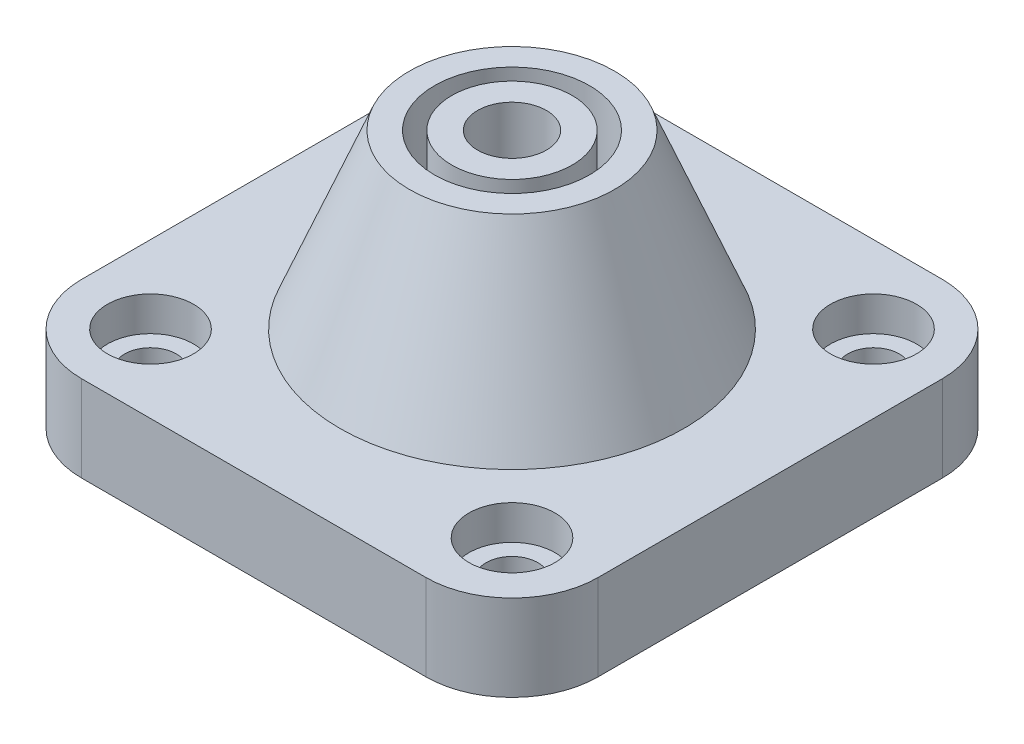
SolidWorks part; units mm, degrees
ref_plane "Front Plane" through (0, 0, 0) normal (0, 0, 1) x (1, 0, 0)
ref_plane "Top Plane" through (0, 0, 0) normal (0, 1, 0) x (1, 0, 0)
ref_plane "Right Plane" through (0, 0, 0) normal (1, 0, 0) x (0, 0, -1)
sketch "Sketch1" plane through (0, 0, 0) normal (0, 1, 0) x (1, 0, 0)
  line L1 (-15, -15) -> (15, -15)
  line L2 (-15, -15) -> (-15, 15)
  line L3 (-15, 15) -> (15, 15)
  line L4 (15, -15) -> (15, 15)
  line L5 (-15, -15) -> (15, 15) construction
  line L6 (-15, 15) -> (15, -15) construction
  point P0 (0, 0)
  dimension "D1" = 30
  dimension "D2" = 30
extrude "Boss-Extrude1" add sketch "Sketch1" along normal blind 5
sketch "Sketch4" plane through (0, 5, 0) normal (0, 1, 0) x (1, 0, 0)
  circle A0 centre (0, 0) radius 10
  dimension "D1" = 20
extrude "Boss-Extrude2" add sketch "Sketch4" along normal blind 10
sketch "Sketch5" plane through (0, 15, 0) normal (0, 1, 0) x (1, 0, 0)
  circle A0 centre (0, 0) radius 2
  dimension "D1" = 4
extrude "Cut-Extrude3" cut sketch "Sketch5" against normal through all both and the other way through all
sketch "Sketch6" plane through (0, 15, 0) normal (0, 1, 0) x (1, 0, 0)
  circle A0 centre (0, 0) radius 3.5
  circle A1 centre (0, 0) radius 4.5
  dimension "D1" = 7
  dimension "D2" = 9
extrude "Cut-Extrude4" cut sketch "Sketch6" against normal blind 7
chamfer "Chamfer1" distance 10 angle 22 1 edges at (0, 15, 10) first distance on face at (0, 15, 10)
sketch "Sketch8" plane through (0, 5, 0) normal (0, 1, 0) x (1, 0, 0)
  line L0 (-10.5, -1001.1158) -> (-10.5, 48998.8842) construction
  line L1 (10.5, -1001.594) -> (10.5, 48998.406) construction
  line L2 (-1000.2391, 10.5) -> (48999.7609, 10.5) construction
  line L3 (-998.9639, -10.5) -> (49001.0361, -10.5) construction
  line L4 (15, 15) -> (-15, 15) construction
  line L5 (-15, -15) -> (15, -15) construction
  line L6 (-15, 15) -> (-15, -15) construction
  line L8 (15, -15) -> (15, 15) construction
  circle A0 centre (10.5, 10.5) radius 1.5
  circle A1 centre (10.5, -10.5) radius 1.5
  circle A2 centre (-10.5, -10.5) radius 1.5
  circle A3 centre (-10.5, 10.5) radius 1.5
  dimension "D6" = 3
  dimension "D8" = 3
  dimension "D10" = 3
  dimension "D12" = 3
  dimension "D1" = 4.5
  dimension "D2" = 4.5
  dimension "D3" = 4.5
  dimension "D4" = 4.5
  dimension "D5" = 0
  dimension "D7" = 0
  dimension "D9" = 0
  dimension "D11" = 0
extrude "Cut-Extrude5" cut sketch "Sketch8" against normal through all both and the other way through all
sketch "Sketch9" plane through (0, 5, 0) normal (0, 1, 0) x (1, 0, 0)
  circle A0 centre (-10.5, 10.5) radius 2.5
  circle A1 centre (10.5, 10.5) radius 2.5
  circle A2 centre (10.5, -10.5) radius 2.5
  circle A3 centre (-10.5, -10.5) radius 2.5
  dimension "D1" = 5
  dimension "D2" = 5
  dimension "D3" = 5
  dimension "D4" = 5
extrude "Cut-Extrude6" cut sketch "Sketch9" against normal blind 2
fillet "Fillet1" radius 5 4 edges at (-15, 2.5, -15) (15, 2.5, -15) (15, 2.5, 15) (-15, 2.5, 15)
chamfer "Chamfer2" distance 7 angle 35 1 edges at (0, 0, 2) first distance on face at (0, 15, 2)
